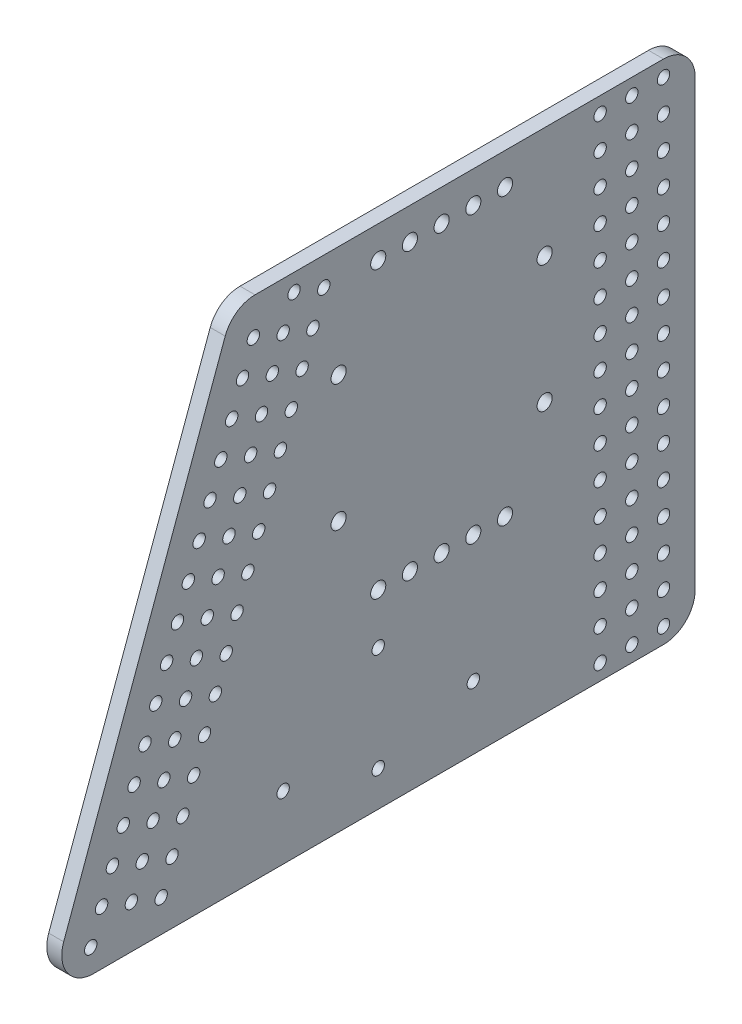
SolidWorks part; units mm, degrees
ref_plane "Front Plane" through (0, 0, 0) normal (0, 0, 1) x (1, 0, 0)
ref_plane "Top Plane" through (0, 0, 0) normal (0, 1, 0) x (1, 0, 0)
ref_plane "Right Plane" through (0, 0, 0) normal (1, 0, 0) x (0, 0, -1)
sketch "Sketch1" plane through (17.7134, 0, 0) normal (1, 0, 0) x (0, 0, -1)
  line L0 (0, 0) -> (259.2252, 0)
  line L1 (221.1252, 6.35) -> (221.1252, 19.05) construction
  line L2 (86.5421, 200.6401) -> (98.4762, 196.2965) construction
  line L3 (259.2252, 0) -> (259.2252, 203.2)
  line L4 (259.2252, 203.2) -> (73.9588, 203.2)
  line L5 (73.9588, 203.2) -> (0, 0)
  line L6 (98.4762, 196.2965) -> (110.4103, 191.9528) construction
  line L7 (82.1984, 188.706) -> (77.8548, 176.7719) construction
  line L8 (86.5421, 200.6401) -> (13.5151, 0) construction
  line L9 (98.4762, 196.2965) -> (27.0301, 0) construction
  line L13 (40.5452, 0) -> (110.4103, 191.9528) construction
  circle A0 centre (246.5252, 6.35) radius 2.4892
  circle A1 centre (233.8252, 6.35) radius 2.4892
  circle A2 centre (221.1252, 6.35) radius 2.4892
  circle A3 centre (221.1252, 19.05) radius 2.4892
  circle A4 centre (246.5252, 19.05) radius 2.4892
  circle A5 centre (233.8252, 19.05) radius 2.4892
  circle A6 centre (221.1252, 31.75) radius 2.4892
  circle A8 centre (98.4762, 196.2965) radius 2.4892
  circle A9 centre (110.4103, 191.9528) radius 2.4892
  circle A10 centre (246.5252, 31.75) radius 2.4892
  circle A11 centre (233.8252, 31.75) radius 2.4892
  circle A12 centre (221.1252, 44.45) radius 2.4892
  circle A13 centre (246.5252, 44.45) radius 2.4892
  circle A14 centre (233.8252, 44.45) radius 2.4892
  circle A15 centre (221.1252, 57.15) radius 2.4892
  circle A16 centre (246.5252, 57.15) radius 2.4892
  circle A17 centre (233.8252, 57.15) radius 2.4892
  circle A18 centre (221.1252, 69.85) radius 2.4892
  circle A19 centre (246.5252, 69.85) radius 2.4892
  circle A20 centre (233.8252, 69.85) radius 2.4892
  circle A21 centre (221.1252, 82.55) radius 2.4892
  circle A22 centre (246.5252, 82.55) radius 2.4892
  circle A23 centre (233.8252, 82.55) radius 2.4892
  circle A24 centre (221.1252, 95.25) radius 2.4892
  circle A25 centre (246.5252, 95.25) radius 2.4892
  circle A26 centre (233.8252, 95.25) radius 2.4892
  circle A27 centre (221.1252, 107.95) radius 2.4892
  circle A28 centre (246.5252, 107.95) radius 2.4892
  circle A29 centre (233.8252, 107.95) radius 2.4892
  circle A30 centre (221.1252, 120.65) radius 2.4892
  circle A31 centre (246.5252, 120.65) radius 2.4892
  circle A32 centre (233.8252, 120.65) radius 2.4892
  circle A33 centre (221.1252, 133.35) radius 2.4892
  circle A34 centre (246.5252, 133.35) radius 2.4892
  circle A35 centre (233.8252, 133.35) radius 2.4892
  circle A36 centre (221.1252, 146.05) radius 2.4892
  circle A37 centre (246.5252, 146.05) radius 2.4892
  circle A38 centre (233.8252, 146.05) radius 2.4892
  circle A39 centre (221.1252, 158.75) radius 2.4892
  circle A40 centre (246.5252, 158.75) radius 2.4892
  circle A41 centre (233.8252, 158.75) radius 2.4892
  circle A42 centre (221.1252, 171.45) radius 2.4892
  circle A43 centre (246.5252, 171.45) radius 2.4892
  circle A44 centre (233.8252, 171.45) radius 2.4892
  circle A45 centre (221.1252, 184.15) radius 2.4892
  circle A46 centre (246.5252, 184.15) radius 2.4892
  circle A47 centre (233.8252, 184.15) radius 2.4892
  circle A48 centre (221.1252, 196.85) radius 2.4892
  circle A49 centre (246.5252, 196.85) radius 2.4892
  circle A50 centre (233.8252, 196.85) radius 2.4892
  circle A51 centre (82.1984, 188.706) radius 2.4892
  circle A52 centre (77.8548, 176.7719) radius 2.4892
  circle A53 centre (94.1325, 184.3624) radius 2.4892
  circle A54 centre (106.0666, 180.0187) radius 2.4892
  circle A55 centre (73.5111, 164.8378) radius 2.4892
  circle A56 centre (89.7889, 172.4283) radius 2.4892
  circle A57 centre (101.723, 168.0846) radius 2.4892
  circle A58 centre (69.1675, 152.9037) radius 2.4892
  circle A59 centre (85.4452, 160.4942) radius 2.4892
  circle A60 centre (97.3793, 156.1505) radius 2.4892
  circle A61 centre (64.8238, 140.9696) radius 2.4892
  circle A62 centre (81.1016, 148.5601) radius 2.4892
  circle A63 centre (93.0357, 144.2164) radius 2.4892
  circle A64 centre (60.4802, 129.0355) radius 2.4892
  circle A65 centre (76.7579, 136.626) radius 2.4892
  circle A66 centre (88.692, 132.2823) radius 2.4892
  circle A67 centre (56.1365, 117.1014) radius 2.4892
  circle A68 centre (72.4142, 124.6919) radius 2.4892
  circle A69 centre (84.3483, 120.3482) radius 2.4892
  circle A70 centre (51.7928, 105.1673) radius 2.4892
  circle A71 centre (68.0706, 112.7578) radius 2.4892
  circle A72 centre (80.0047, 108.4141) radius 2.4892
  circle A73 centre (47.4492, 93.2332) radius 2.4892
  circle A74 centre (63.7269, 100.8237) radius 2.4892
  circle A75 centre (75.661, 96.48) radius 2.4892
  circle A76 centre (43.1055, 81.2992) radius 2.4892
  circle A77 centre (59.3833, 88.8896) radius 2.4892
  circle A78 centre (71.3174, 84.5459) radius 2.4892
  circle A79 centre (38.7619, 69.3651) radius 2.4892
  circle A80 centre (55.0396, 76.9555) radius 2.4892
  circle A81 centre (66.9737, 72.6118) radius 2.4892
  circle A82 centre (34.4182, 57.431) radius 2.4892
  circle A83 centre (50.696, 65.0214) radius 2.4892
  circle A84 centre (62.6301, 60.6777) radius 2.4892
  circle A85 centre (30.0746, 45.4969) radius 2.4892
  circle A86 centre (46.3523, 53.0873) radius 2.4892
  circle A87 centre (58.2864, 48.7436) radius 2.4892
  circle A88 centre (25.7309, 33.5628) radius 2.4892
  circle A89 centre (42.0087, 41.1532) radius 2.4892
  circle A90 centre (53.9428, 36.8095) radius 2.4892
  circle A91 centre (21.3872, 21.6287) radius 2.4892
  circle A92 centre (37.665, 29.2191) radius 2.4892
  circle A93 centre (49.5991, 24.8755) radius 2.4892
  circle A94 centre (17.0436, 9.6946) radius 2.4892
  circle A95 centre (33.3213, 17.285) radius 2.4892
  circle A96 centre (45.2554, 12.9414) radius 2.4892
  dimension "D8" = 12.7
  dimension "D2" = 259.2252
  dimension "D4" = 12.7
  dimension "D10" = 12.7
  dimension "D11" = 12.7
  dimension "D7" = 12.7
  dimension "D14" = 11.2472
  dimension "D15" = 16
  dimension "D16" = 4.9784
  dimension "D1" = 203.2
  dimension "D5" = 12.7
  dimension "D9" = 185.2664
  dimension "D3" = 12.7
  dimension "D6" = 6.35
  dimension "D13" = 12.7
  dimension "D17" = 12.7
  dimension "D12" = 16
extrude "Boss-Extrude1" add sketch "Sketch1" along normal blind 6 contours L4 L5 L0 L3 region at (17.7134, 95.6955, -146.9878)
fillet "Fillet1" radius 12.7 4 edges at (20.7134, 203.2, -259.2252) (20.7134, 0, -259.2252) (20.7134, 203.2, -73.9588) (20.7134, 0, 0)
sketch "Sketch4" plane through (17.7134, 0, 0) normal (-1, 0, 0) x (0, 0, 1)
  line L0 (-246.5252, 203.2) -> (-82.8514, 203.2) construction
  line L1 (-183.0252, 190.5) -> (-170.3252, 190.5) construction
  line L2 (-183.0252, 190.5) -> (-183.0252, 76.2) construction
  line L3 (-198.9002, 107.95) -> (-198.9002, 158.75) construction
  circle A0 centre (-183.0252, 190.5) radius 3.0309
  circle A2 centre (-170.3252, 190.5) radius 3.0309
  circle A3 centre (-157.6252, 190.5) radius 3.0309
  circle A4 centre (-144.9252, 190.5) radius 3.0309
  circle A5 centre (-183.0252, 76.2) radius 3.0309
  circle A6 centre (-170.3252, 76.2) radius 3.0309
  circle A7 centre (-157.6252, 76.2) radius 3.0309
  circle A8 centre (-144.9252, 76.2) radius 3.0309
  circle A9 centre (-132.2252, 190.5) radius 3.0309
  circle A10 centre (-132.2252, 76.2) radius 3.0309
  circle A11 centre (-221.1252, 184.15) radius 2.4892 construction
  circle A12 centre (-198.9002, 158.75) radius 3.0309
  circle A13 centre (-198.9002, 107.95) radius 3.0309
  circle A14 centre (-116.3502, 158.75) radius 3.0309
  circle A15 centre (-116.3502, 107.95) radius 3.0309
  point P34 (-198.9002, 133.35)
  dimension "D1" = 12.7
  dimension "D2" = 6.0617
  dimension "D3" = 5
  dimension "D6" = 38.1
  dimension "D8" = 50.8
  dimension "D9" = 82.55
  dimension "D10" = 15.875
  dimension "D11" = 57.15
  dimension "D4" = 12.7
  dimension "D7" = 114.3
  dimension "D5" = 2
extrude "Cut-Extrude1" cut sketch "Sketch4" against normal through all
sketch "Sketch5" plane through (17.7134, 0, 0) normal (-1, 0, 0) x (0, 0, 1)
  line L0 (-170.3252, 25.4) -> (-94.1252, 25.4) construction
  line L2 (-259.2252, 12.7) -> (-259.2252, 190.5) construction
  line L3 (-18.1375, 0) -> (-246.5252, 0) construction
  circle A0 centre (-170.3252, 25.4) radius 2.4892
  circle A1 centre (-94.1252, 25.4) radius 2.4892
  circle A2 centre (-132.2252, 56.134) radius 2.4892
  circle A3 centre (-132.2252, 14.224) radius 2.4892
  dimension "D1" = 76.2
  dimension "D2" = 4.9784
  dimension "D5" = 38.1
  dimension "D7" = 30.734
  dimension "D3" = 88.9
  dimension "D4" = 25.4
  dimension "D6" = 11.176
extrude "Cut-Extrude2" cut sketch "Sketch5" against normal through all
sketch "Sketch6" plane through (23.7134, 0, 0) normal (1, 0, 0) x (0, 0, -1)
  line L0 (259.2252, -983.9832) -> (259.2252, 49016.0168) construction
  line L2 (-782.2087, 0) -> (49217.7913, 0) construction
  line L3 (259.2252, 12.7) -> (259.2252, 190.5) construction
  line L4 (18.1375, 0) -> (246.5252, 0) construction
  point P3 (259.2252, 0)
